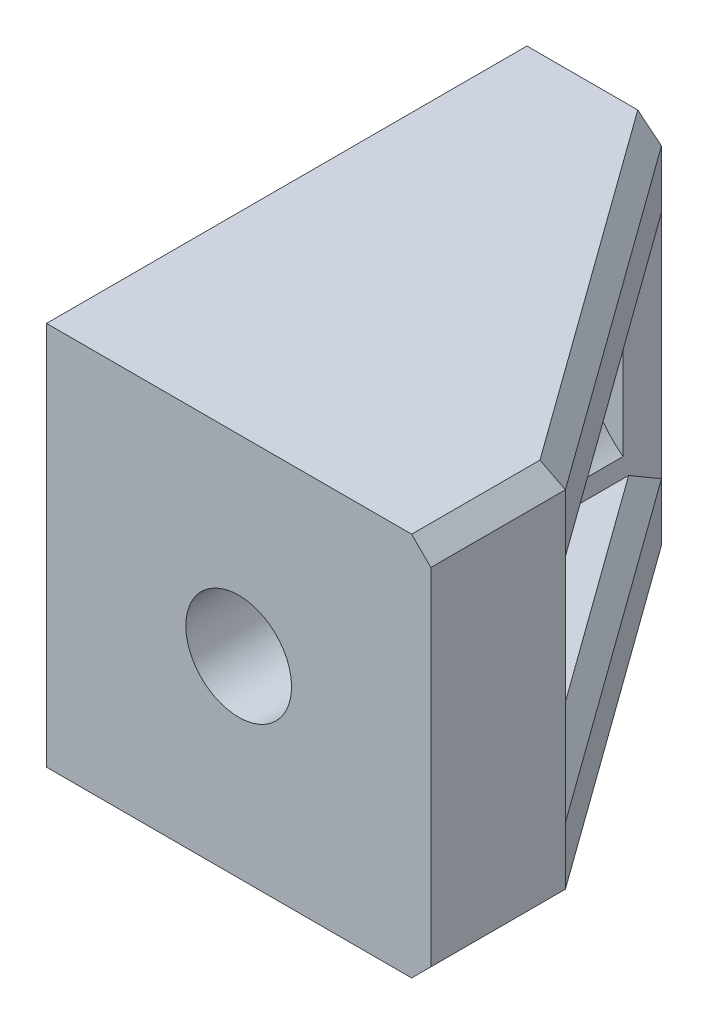
SolidWorks part; units mm, degrees
ref_plane "Front Plane" through (0, 0, 0) normal (0, 0, 1) x (1, 0, 0)
ref_plane "Top Plane" through (0, 0, 0) normal (0, 1, 0) x (1, 0, 0)
ref_plane "Right Plane" through (0, 0, 0) normal (1, 0, 0) x (0, 0, -1)
sketch "Sketch2" plane through (0, -457.6383, -1.4123) normal (0, 1, 0) x (1, 0, 0)
  line L1 (25.5057, -2.1814) -> (32.5057, -2.1814)
  line L2 (25.5057, -2.1814) -> (25.5057, -27.1814)
  line L3 (25.5057, -27.1814) -> (45.5057, -27.1814)
  line L4 (45.5057, -20.1814) -> (45.5057, -27.1814)
  line L5 (45.5057, -20.1814) -> (32.5057, -20.1814)
  line L6 (32.5057, -20.1814) -> (32.5057, -2.1814)
  dimension "D1" = 7
  dimension "D2" = 7
  dimension "D3" = 25
  dimension "D4" = 20
extrude "main" add sketch "Sketch2" along normal blind 20
sketch "Sketch3" plane through (32.5057, 0, 0) normal (1, 0, 0) x (0, 0, -1)
  line L0 (-25.7692, -437.6383) -> (-25.7692, -457.6383) construction
  line L1 (-18.7692, -447.6383) -> (8.6195, -447.6383) construction
  line L2 (-18.7692, -437.6383) -> (-18.7692, -457.6383) construction
  circle A0 centre (-6.7692, -447.6383) radius 2.25
  dimension "D2" = 4.5
  dimension "D1" = 19
extrude "screw_hole" cut sketch "Sketch3" against normal through all
sketch "screw_cut" plane through (0, 0, 18.7692) normal (0, 0, -1) x (-1, 0, 0)
  circle A0 centre (-35.5057, -447.6383) radius 5
  dimension "D1" = 10
sketch "Sketch4" plane through (0, 0, 18.7692) normal (0, 0, -1) x (-1, 0, 0)
  line L2 (-45.5057, -437.6383) -> (-45.5057, -457.6383) construction
  line L3 (-45.5057, -447.6383) -> (-32.5057, -447.6383) construction
  line L4 (-32.5057, -437.6383) -> (-32.5057, -457.6383) construction
  circle A0 centre (-35.5057, -447.6383) radius 2.75
  circle A1 centre (-35.5057, -447.6383) radius 5 construction
  dimension "D2" = 5.5
extrude "screw_hole_2" cut sketch "Sketch4" against normal through all
extrude "screwcut" cut sketch "screw_cut" along normal blind 16
sketch "Sketch7" plane through (25.5057, 0, 0) normal (-1, 0, 0) x (0, 0, 1)
  circle A0 centre (6.7692, -447.6383) radius 4
  dimension "D1" = 8
extrude "Cut-Extrude7" cut sketch "Sketch7" against normal blind 5 from offset 5 offset against normal yes
sketch "Sketch8" plane through (0, -457.6383, 0) normal (0, -1, 0) x (1, 0, 0)
  line L0 (32.5057, 0.7692) -> (45.5057, 18.7692)
rib "Rib3" sketch "Sketch8" sketch "Sketch8" thickness 5 extrusion direction parallel to sketch draft on no parameters "D1"=5
sketch "Sketch9" plane through (0, -437.6383, 0) normal (0, 1, 0) x (1, 0, 0)
  line L0 (32.5057, -0.7692) -> (45.5057, -18.7692)
rib "Rib4" sketch "Sketch9" sketch "Sketch9" thickness 5 extrusion direction parallel to sketch draft on no parameters "D1"=5
chamfer "Chamfer1" distance 1 angle 45 6 edges at (39.0057, -437.6383, 9.7692) (45.5057, -437.6383, 22.2692) (39.0057, -457.6383, 9.7692) (45.5057, -457.6383, 22.2692) (39.0057, -452.6383, 9.7692) (39.0057, -442.6383, 9.7692)
